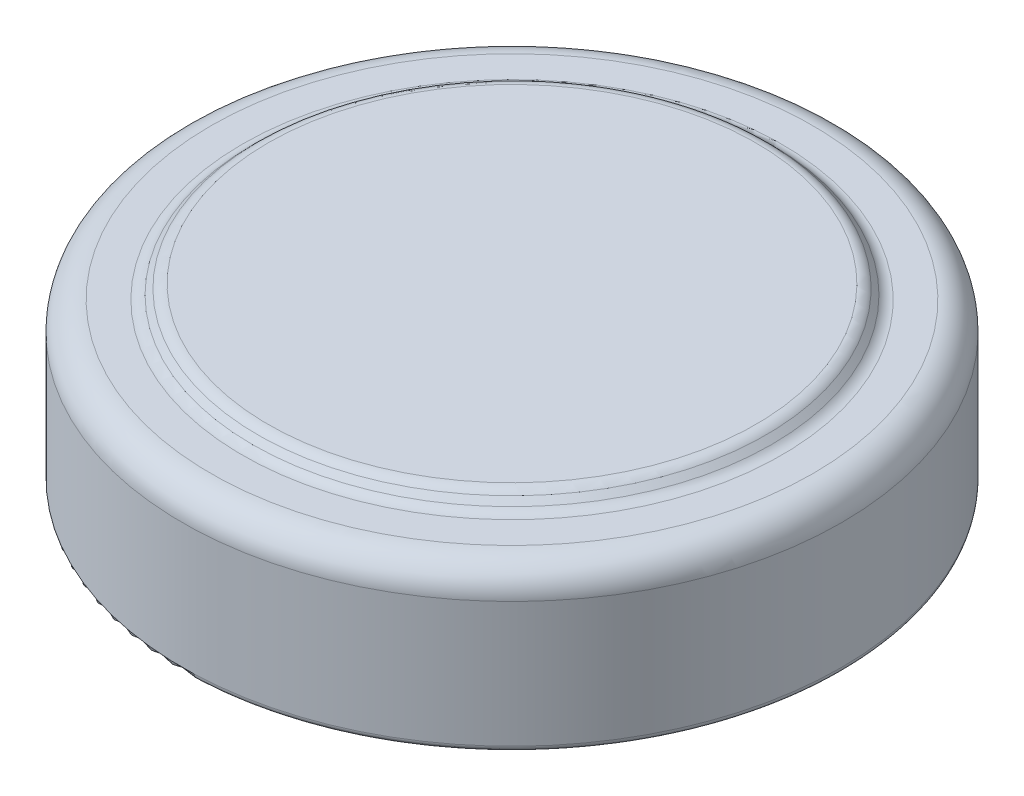
SolidWorks part; units mm, degrees
ref_plane "Front Plane" through (0, 0, 0) normal (0, 0, 1) x (1, 0, 0)
ref_plane "Top Plane" through (0, 0, 0) normal (0, 1, 0) x (1, 0, 0)
ref_plane "Right Plane" through (0, 0, 0) normal (1, 0, 0) x (0, 0, -1)
sketch "Sketch1" plane through (0, 0, 0) normal (0, 0, 1) x (1, 0, 0)
  line L0 (0, 0) -> (-5.7, 0)
  line L1 (-5.8, 0.1) -> (-5.8, 2.306)
  line L2 (-4.2924, 3.05) -> (0, 3.05)
  line L3 (0, 3.05) -> (0, 0)
  line L4 (-4.4692, 2.9768) -> (-4.5668, 2.8792)
  line L7 (-5.3, 2.806) -> (-4.7436, 2.806)
  arc A0 (-5.8, 2.306) -> (-5.3, 2.806) centre (-5.3, 2.306) cw
  arc A1 (-4.2924, 3.05) -> (-4.4692, 2.9768) centre (-4.2924, 2.8) ccw
  arc A2 (-4.7436, 2.806) -> (-4.5668, 2.8792) centre (-4.7436, 3.056) ccw
  arc A3 (-5.7, 0) -> (-5.8, 0.1) centre (-5.7, 0.1) cw
  point P9 (-5.8, 2.806)
  point P14 (-4.64, 2.806)
  point P17 (-5.8, 0)
  dimension "D6" = 0.5
  dimension "D7" = 0.25
  dimension "D8" = 0.1
  dimension "D1" = 5.8
  dimension "D2" = 3.05
  dimension "D3" = 4.64
  dimension "D4" = 2.806
  dimension "D5" = 45
revolve "Revolve1" add sketch "Sketch1" angle 360 about L3
sketch "Sketch2" plane through (0, 0, 0) normal (0, -1, 0) x (1, 0, 0)
  line L0 (0.25, -0.25) -> (0.25, -2)
  line L1 (-0.25, 2) -> (0.25, 2)
  line L2 (-0.25, 2) -> (-0.25, 0.25)
  line L3 (-0.25, -2) -> (0.25, -2)
  line L4 (0.25, 2) -> (0.25, 0.25)
  line L5 (-2, 0.25) -> (-0.25, 0.25)
  line L6 (-2, 0.25) -> (-2, -0.25)
  line L7 (-2, -0.25) -> (-0.25, -0.25)
  line L8 (2, 0.25) -> (2, -0.25)
  line L9 (-0.25, -0.25) -> (-0.25, -2)
  line L10 (0.25, 0.25) -> (2, 0.25)
  line L11 (0.25, -0.25) -> (2, -0.25)
  circle A0 centre (0, 0) radius 4 construction
  text T0 "                                SR54" font "Century Gothic" height 1
  dimension "D1" = 8
  dimension "D2" = 0.5
  dimension "D3" = 0.5
  dimension "D4" = 0.25
  dimension "D5" = 0.25
  dimension "D6" = 4
  dimension "D7" = 2
  dimension "D8" = 2
  dimension "D9" = 4
wrap "Wrap1" sketch "Sketch2" wrap type scribe source sketch "Sketch2" face at (-5.7, 0, 0)
